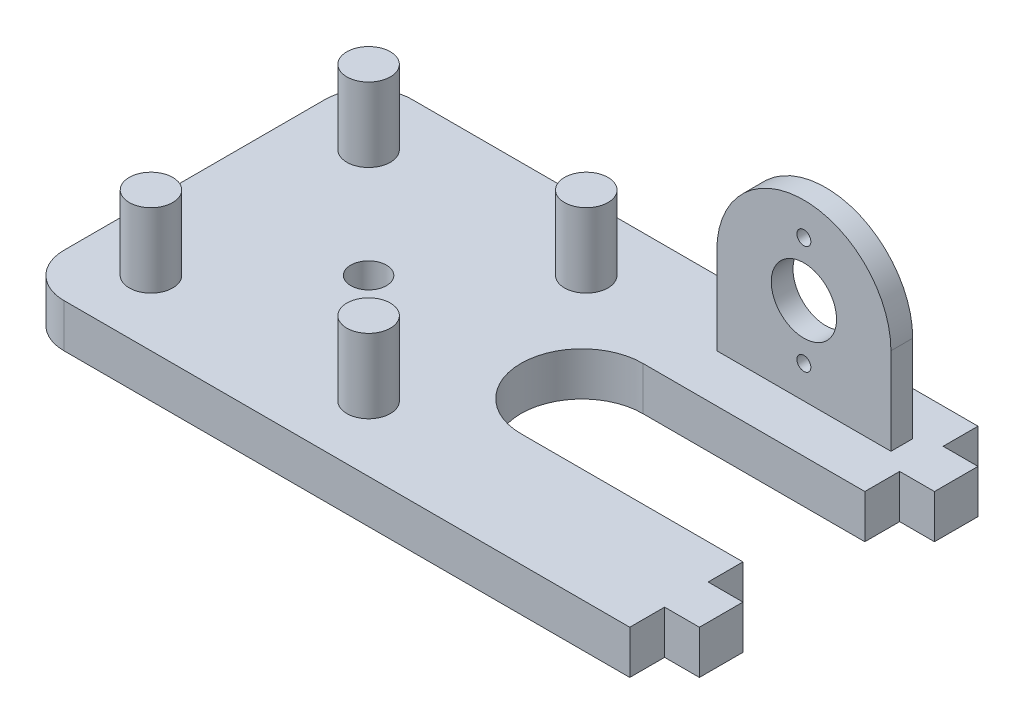
SolidWorks part; units mm, degrees
ref_plane "正面" through (0, 0, 0) normal (0, 0, 1) x (1, 0, 0)
ref_plane "平面" through (0, 0, 0) normal (0, 1, 0) x (1, 0, 0)
ref_plane "右側面" through (0, 0, 0) normal (1, 0, 0) x (0, 0, -1)
sketch "ｽｹｯﾁ1" plane through (0, 0, 0) normal (0, 1, 0) x (1, 0, 0)
  line L0 (70, 14) -> (70, 40)
  line L1 (-70, -40) -> (70, -40)
  line L2 (-70, -40) -> (-70, 40)
  line L3 (-70, 40) -> (70, 40)
  line L4 (70, -40) -> (70, -14)
  line L5 (-70, -40) -> (70, 40) construction
  line L6 (-70, 40) -> (70, -40) construction
  line L7 (70, 14) -> (5, 14)
  line L9 (70, -14) -> (5, -14)
  line L10 (5, 14) -> (5, -14)
  line L11 (-70, 40) -> (35285.3391, -35315.3391) construction
  line L12 (-70, -40) -> (35285.3391, 35315.3391) construction
  circle A0 centre (-30, 0) radius 4.1
  point P0 (0, 0)
  point P12 (0, 0)
  point P17 (-30, 0)
  point P18 (0, 0)
  point P19 (-42.5, 0)
  point P20 (-55.6919, 0)
  point P21 (0, 0)
  dimension "D5" = 8.2
  dimension "D1" = 80
  dimension "D2" = 140
  dimension "D3" = 28
  dimension "D4" = 65
  dimension "D6" = 45
  dimension "D7" = 45
extrude "ﾎﾞｽ - 押し出し1" add sketch "ｽｹｯﾁ1" along normal blind 10
sketch "ｽｹｯﾁ2" plane through (0, 10, 0) normal (0, 1, 0) x (1, 0, 0)
  line L2 (-70, 40) -> (10, -40) construction
  line L4 (70, 40) -> (-70, 40) construction
  circle A0 centre (-55, 25) radius 5
  circle A1 centre (-5, 25) radius 5
  circle A2 centre (-5, -25) radius 5
  circle A3 centre (-55, -25) radius 5
  point P9 (0, 0)
  dimension "D1" = 10
  dimension "D2" = 50
  dimension "D3" = 50
  dimension "D4" = 25
  dimension "D5" = 45
extrude "ﾎﾞｽ - 押し出し2" add sketch "ｽｹｯﾁ2" along normal blind 17
fillet "ﾌｨﾚｯﾄ1" radius 10 2 edges at (-70, 5, -40) (-70, 5, 40)
fillet "ﾌｨﾚｯﾄ2" 2 edges at (5, 5, 14) (5, 5, -14) type full round first side face at (37.5, 5, 14) second side face at (37.5, 5, -14) middle face at (5, 5, 0)
sketch "ｽｹｯﾁ4" plane through (70, 0, 0) normal (1, 0, 0) x (0, 0, -1)
  line L0 (-40, 0) -> (-14, 0) construction
  line L1 (-32, 0) -> (-22, 0)
  line L2 (-32, 0) -> (-32, 10)
  line L3 (-32, 10) -> (-22, 10)
  line L4 (-22, 0) -> (-22, 10)
  line L5 (-40, 10) -> (-14, 10) construction
  line L6 (14, 0) -> (40, 0) construction
  line L7 (22, 0) -> (32, 0)
  line L8 (22, 0) -> (22, 10)
  line L9 (22, 10) -> (32, 10)
  line L10 (32, 0) -> (32, 10)
  line L11 (14, 10) -> (40, 10) construction
  point P16 (-27, 0)
  point P17 (-27, 0)
  point P18 (27, 0)
  point P19 (27, 0)
extrude "ﾎﾞｽ - 押し出し3" add sketch "ｽｹｯﾁ4" along normal blind 8
sketch "ｽｹｯﾁ5" plane through (0, 10, 0) normal (0, 1, 0) x (1, 0, 0)
  line L1 (65, 25) -> (25, 25)
  line L2 (65, 25) -> (65, 30)
  line L3 (65, 30) -> (25, 30)
  line L4 (25, 25) -> (25, 30)
  line L5 (19, 14) -> (70, 14) construction
  line L6 (70, 14) -> (70, 22) construction
  dimension "D1" = 5
  dimension "D2" = 40
  dimension "D3" = 11
  dimension "D4" = 5
extrude "ﾎﾞｽ - 押し出し4" add sketch "ｽｹｯﾁ5" along normal blind 40
fillet "ﾌｨﾚｯﾄ3" 2 edges at (65, 50, -27.5) (25, 50, -27.5) type full round first side face at (65, 30, -27.5) second side face at (25, 30, -27.5) middle face at (45, 50, -27.5)
sketch "ｽｹｯﾁ6" plane through (0, 0, -25) normal (0, 0, 1) x (1, 0, 0)
  circle A0 centre (45, 30) radius 7.5
  circle A1 centre (45, 42.5) radius 1.6
  circle A2 centre (45, 17.5) radius 1.6
  arc A4 (65, 30) -> (25, 30) centre (45, 30) ccw construction
  point P6 (0, 0)
  point P7 (51.058, 40.0148)
  dimension "D2" = 15
  dimension "D3" = 3.2
  dimension "D1" = 25
  dimension "D4" = 12.5
extrude "ｶｯﾄ - 押し出し1" cut sketch "ｽｹｯﾁ6" against normal through all
